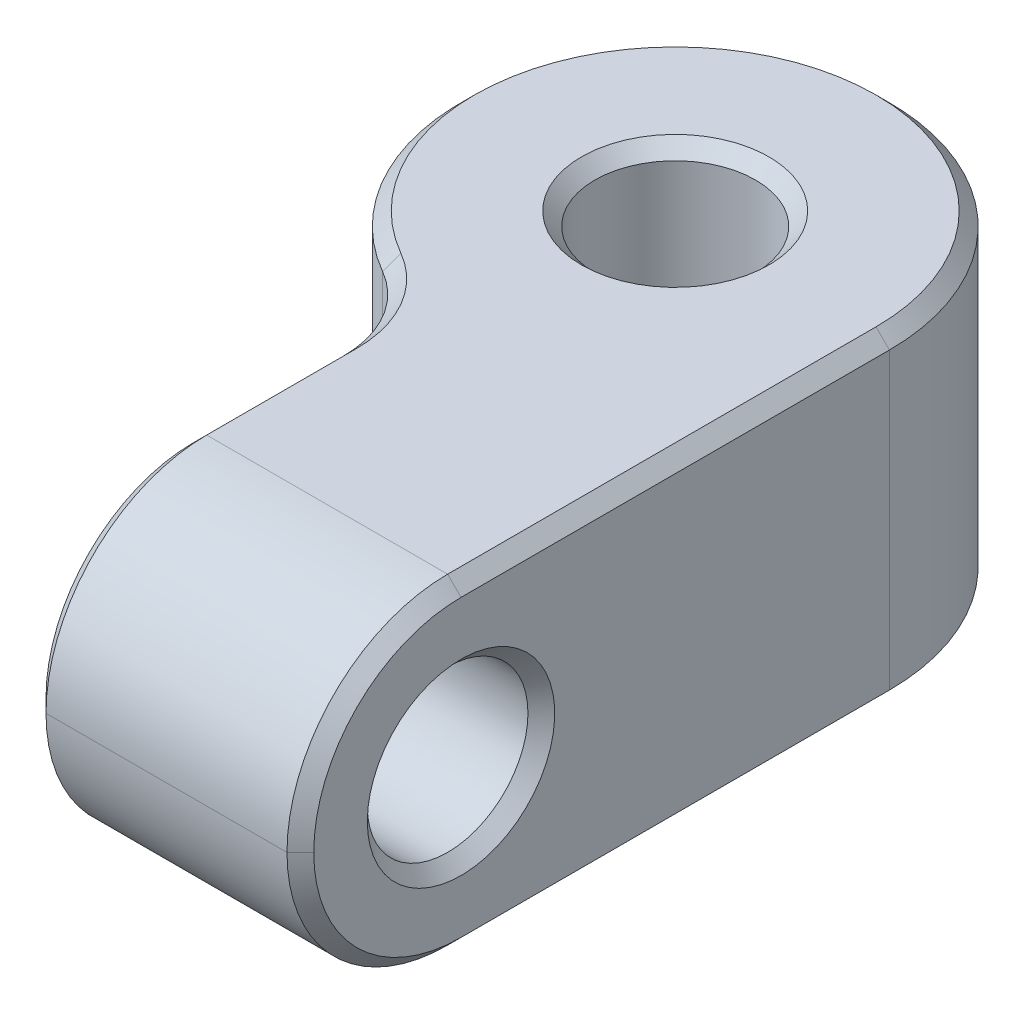
SolidWorks part; units mm, degrees
ref_plane "Front Plane" through (0, 0, 0) normal (0, 0, 1) x (1, 0, 0)
ref_plane "Top Plane" through (0, 0, 0) normal (0, 1, 0) x (1, 0, 0)
ref_plane "Right Plane" through (0, 0, 0) normal (1, 0, 0) x (0, 0, -1)
sketch "Sketch1" plane through (0, 0, 0) normal (0, 1, 0) x (1, 0, 0)
  line L0 (-1.5875, -17.4625) -> (-1.5875, -6.1484)
  line L5 (-1.5875, -17.4625) -> (6.35, -17.4625)
  line L6 (6.35, -17.4625) -> (6.35, 0)
  circle A0 centre (0, 0) radius 2.3813
  arc A1 (6.35, 0) -> (-1.5875, -6.1484) centre (0, 0) ccw
  dimension "D1" = 4.7625
  dimension "D2" = 12.7
  dimension "D3" = 1.5875
  dimension "D4" = 17.4625
extrude "Boss-Extrude1" add sketch "Sketch1" along normal blind 9.525
sketch "Sketch5" plane through (6.35, 0, 0) normal (1, 0, 0) x (0, 0, -1)
  line L0 (-17.4625, 0) -> (0, 0) construction
  circle A0 centre (-12.7, 4.7625) radius 2.3813
  dimension "D3" = 4.7625
  dimension "D1" = 12.7
  dimension "D2" = 4.7625
extrude "Cut-Extrude3" cut sketch "Sketch5" against normal through all both and the other way through all
fillet "Fillet1" radius 4.7625 2 edges at (2.3812, 0, 17.4625) (2.3812, 9.525, 17.4625)
fillet "Fillet2" radius 3.175 1 edges at (-1.5875, 4.7625, 6.1484)
chamfer "Chamfer1" distance 0.3969 angle 45 16 edges at (6.35, 4.7625, 15.0812) (-1.5875, 4.7625, 10.3187) (0, 9.525, 2.3813) (-3.175, 0, -5.4993) (-2.0129, 0, 6.6614) (6.35, 0, 6.35) (-1.5875, 0, 10.4744) (6.35, 1.3949, 16.0676) (-1.5875, 1.3949, 16.0676) (6.35, 8.1301, 16.0676) (-1.5875, 8.1301, 16.0676) (6.35, 9.525, 6.35) (-1.5875, 9.525, 10.4744) (-2.0129, 9.525, 6.6614) (-3.175, 9.525, -5.4993) (0, 0, 2.3813)
